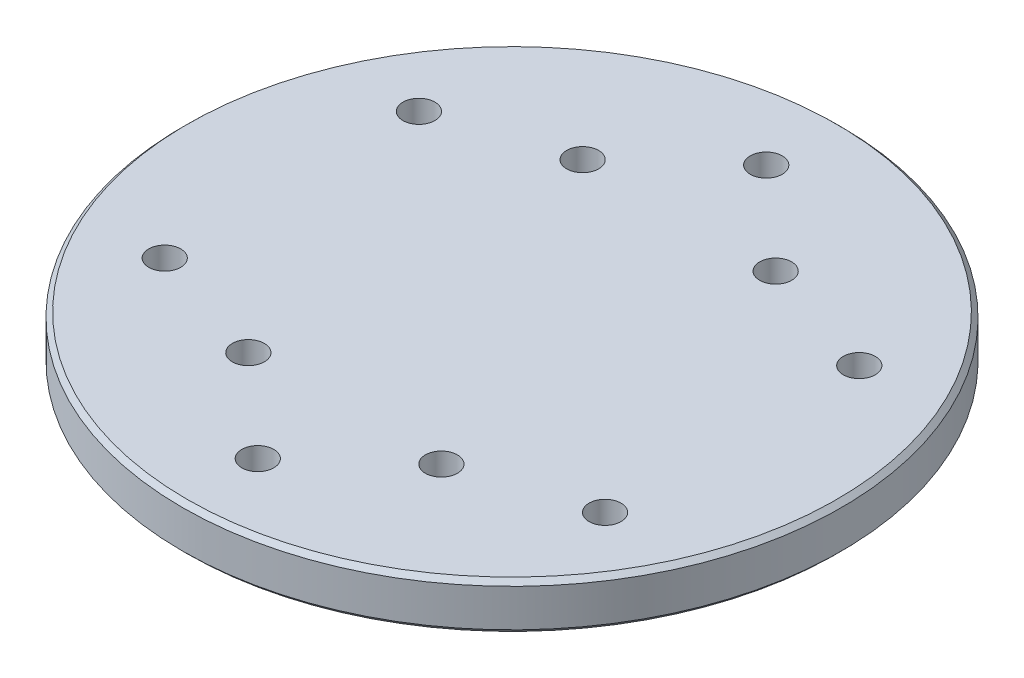
SolidWorks part; units mm, degrees
ref_plane "Front Plane" through (0, 0, 0) normal (0, 0, 1) x (1, 0, 0)
ref_plane "Top Plane" through (0, 0, 0) normal (0, 1, 0) x (1, 0, 0)
ref_plane "Right Plane" through (0, 0, 0) normal (1, 0, 0) x (0, 0, -1)
sketch "Sketch1" plane through (0, 0, 0) normal (0, 1, 0) x (1, 0, 0)
  circle A0 centre (0, 0) radius 70
  dimension "D1" = 140
extrude "Boss-Extrude1" add sketch "Sketch1" along normal blind 10
chamfer "Chamfer1" distance 1 angle 45 2 edges at (0, 0, 70) (0, 10, 70)
sketch "Sketch2" plane through (0, 10, 0) normal (0, 1, 0) x (1, 0, 0)
  line L0 (0, 0) -> (0, 54) construction
  line L1 (0, 0) -> (46.7654, 27) construction
  line L3 (-20.5, 35.5) -> (20.5, 35.5) construction
  line L4 (-20.5, 35.5) -> (-20.5, -35.5) construction
  line L5 (-20.5, -35.5) -> (20.5, -35.5) construction
  line L6 (20.5, 35.5) -> (20.5, -35.5) construction
  line L7 (-20.5, 35.5) -> (20.5, -35.5) construction
  line L8 (-20.5, -35.5) -> (20.5, 35.5) construction
  circle A0 centre (0, 0) radius 54 construction
  circle A1 centre (0, 54) radius 3.4
  circle A2 centre (46.7654, 27) radius 3.4
  circle A3 centre (46.7654, -27) radius 3.4
  circle A4 centre (0, -54) radius 3.4
  circle A5 centre (-46.7654, -27) radius 3.4
  circle A6 centre (-46.7654, 27) radius 3.4
  circle A7 centre (-20.5, 35.5) radius 3.4
  circle A8 centre (20.5, -35.5) radius 3.4
  circle A9 centre (-20.5, -35.5) radius 3.4
  circle A10 centre (20.5, 35.5) radius 3.4
  point P18 (0, 0)
  point P22 (0, 0)
  point P29 (0, 0)
  point P30 (0, 0)
  point P31 (0, 0)
  dimension "D1" = 108
  dimension "D2" = 6.8
  dimension "D4" = 60
  dimension "D5" = 71
  dimension "D6" = 41
  dimension "D3" = 6
extrude "Cut-Extrude1" cut sketch "Sketch2" against normal through all
